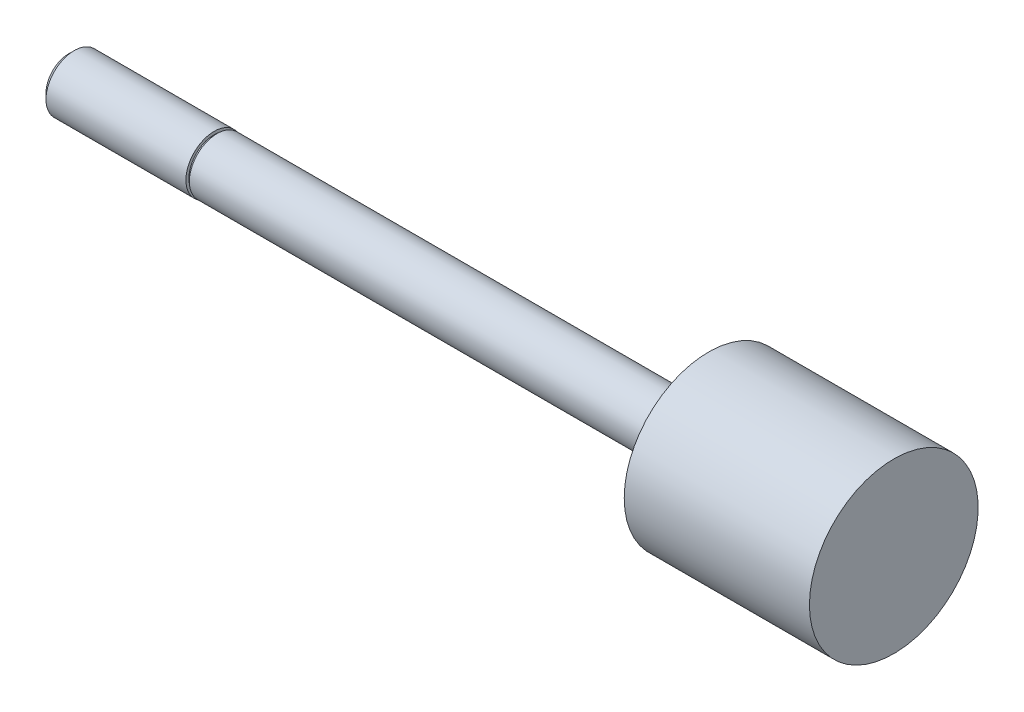
SolidWorks part; units mm, degrees
material "AISI 304"
ref_plane "Front Plane" through (0, 0, 0) normal (0, 0, 1) x (1, 0, 0)
ref_plane "Top Plane" through (0, 0, 0) normal (0, 1, 0) x (1, 0, 0)
ref_plane "Right Plane" through (0, 0, 0) normal (1, 0, 0) x (0, 0, -1)
sketch "Sketch1" plane through (0, 0, 0) normal (0, 0, 1) x (1, 0, 0)
  line L0 (0, 0) -> (0, 2.3749)
  line L1 (0, 2.3749) -> (42.0624, 2.3749)
  line L2 (42.0624, 2.3749) -> (42.0624, 7.2199)
  line L3 (42.0624, 7.2199) -> (57.912, 7.2199)
  line L4 (57.912, 7.2199) -> (57.912, 0)
  line L5 (57.912, 0) -> (0, 0)
  line L6 (57.912, 0) -> (0, 0) construction
revolve "Revolve1" add sketch "Sketch1" angle 360 about L6 reverse direction yes
sketch "Sketch2" plane through (0, 0, 0) normal (0, 0, 1) x (1, 0, 0)
  line L0 (-12.7, 0) -> (-12.7, 1.9406)
  line L1 (-12.7, 1.9406) -> (-12.2276, 2.413)
  line L2 (-12.2276, 2.413) -> (0, 2.413)
  line L3 (0, 2.413) -> (0, 0)
  line L4 (0, 0) -> (-12.7, 0)
  line L5 (0, 0) -> (-12.7, 0) construction
revolve "Revolve2" add sketch "Sketch2" angle 360 about L5 reverse direction yes
cosmetic thread "Cosmetic Thread1"
ref_plane "Plane1" through (0, 0, 0) normal (1, 0, 0) x (0, 0, -1)
ref_plane "Plane2" through (0, 0, 0) normal (1, 0, 0) x (0, 0, -1)
ref_plane "Plane3" through (99.9744, 0, 0) normal (1, 0, 0) x (0, 0, -1)
ref_plane "Plane4" through (-12.7, 0, 0) normal (1, 0, 0) x (0, 0, -1)
sketch "Sketch3" plane through (0, 0, 0) normal (0, 0, 1) x (1, 0, 0)
  line L0 (-0.254, 2.159) -> (0, 2.159)
  line L1 (0, 2.159) -> (0, 2.667)
  line L2 (0, 2.667) -> (-0.254, 2.667)
  line L3 (-0.254, 2.667) -> (-0.254, 2.159)
  line L4 (0, 0) -> (-0.254, 0) construction
revolve "Cut-Revolve1" cut sketch "Sketch3" angle 360 about L4 reverse direction yes
ref_plane "Plane5" through (0, 0, 0) normal (1, 0, 0) x (0, 0, -1)
ref_plane "Plane6" through (-12.7, 0, 0) normal (1, 0, 0) x (0, 0, -1)
ref_plane "dia1 XY" through (0, 0, 0) normal (1, 0, 0) x (0, 0, -1)
ref_plane "dia1 XZ" through (0, 2.3749, 0) normal (0, -1, 0) x (-1, 0, 0)
ref_plane "dia1 YZ" through (0, 0, 0) normal (0, 0, -1) x (-1, 0, 0)
ref_axis "dia1 X" through (0, 2.3749, 80.9) along (0, 0, -1)
ref_axis "dia1 Y" through (0, -50, 0) along (0, 1, 0)
ref_axis "dia1 Z" through (80.9, 2.3749, 0) along (-1, 0, 0)
sketch3d "dia1"
  point P0 (0, 2.3749, 0)
ref_plane "dia12 XY" through (0, 0, 0) normal (1, 0, 0) x (0, 0, -1)
ref_plane "dia12 XZ" through (0, 0, 0) normal (0, -1, 0) x (-1, 0, 0)
ref_plane "dia12 YZ" through (0, 0, 7.8105) normal (0, 0, -1) x (-1, 0, 0)
ref_axis "dia12 X" through (0, 0, 80.9) along (0, 0, -1)
ref_axis "dia12 Y" through (0, -50, 7.8105) along (0, 1, 0)
ref_axis "dia12 Z" through (80.9, 0, 7.8105) along (-1, 0, 0)
sketch3d "dia12"
  point P0 (0, 0, 7.8105)
ref_plane "dia2 XY" through (0, 0, 0) normal (1, 0, 0) x (0, 0, -1)
ref_plane "dia2 XZ" through (0, -2.3749, 0) normal (0, -1, 0) x (-1, 0, 0)
ref_plane "dia2 YZ" through (0, 0, 0) normal (0, 0, -1) x (-1, 0, 0)
ref_axis "dia2 X" through (0, -2.3749, 80.9) along (0, 0, -1)
ref_axis "dia2 Y" through (0, -50, 0) along (0, 1, 0)
ref_axis "dia2 Z" through (80.9, -2.3749, 0) along (-1, 0, 0)
sketch3d "dia2"
  point P0 (0, -2.3749, 0)
ref_plane "dia22 XY" through (0, 0, 0) normal (1, 0, 0) x (0, 0, -1)
ref_plane "dia22 XZ" through (0, 0, 0) normal (0, -1, 0) x (-1, 0, 0)
ref_plane "dia22 YZ" through (0, 0, -7.8105) normal (0, 0, -1) x (-1, 0, 0)
ref_axis "dia22 X" through (0, 0, 80.9) along (0, 0, -1)
ref_axis "dia22 Y" through (0, -50, -7.8105) along (0, 1, 0)
ref_axis "dia22 Z" through (80.9, 0, -7.8105) along (-1, 0, 0)
sketch3d "dia22"
  point P0 (0, 0, -7.8105)
ref_plane "rl1 XY" through (-12.7, 0, 0) normal (1, 0, 0) x (0, 0, -1)
ref_plane "rl1 XZ" through (0, 0, 0) normal (0, -1, 0) x (-1, 0, 0)
ref_plane "rl1 YZ" through (0, 0, 0) normal (0, 0, -1) x (-1, 0, 0)
ref_axis "rl1 X" through (-12.7, 0, 80.9) along (0, 0, -1)
ref_axis "rl1 Y" through (-12.7, -50, 0) along (0, 1, 0)
ref_axis "rl1 Z" through (80.9, 0, 0) along (-1, 0, 0)
sketch3d "rl1"
  point P0 (-12.7, 0, 0)
ref_plane "rl2 XY" through (0, 0, 0) normal (1, 0, 0) x (0, 0, -1)
ref_plane "rl2 XZ" through (0, 0, 0) normal (0, -1, 0) x (-1, 0, 0)
ref_plane "rl2 YZ" through (0, 0, 0) normal (0, 0, -1) x (-1, 0, 0)
ref_axis "rl2 X" through (0, 0, 80.9) along (0, 0, -1)
ref_axis "rl2 Y" through (0, -50, 0) along (0, 1, 0)
ref_axis "rl2 Z" through (80.9, 0, 0) along (-1, 0, 0)
sketch3d "rl2"
  point P0 (0, 0, 0)
ref_plane "rod_cp XY" through (0, 0, 0) normal (1, 0, 0) x (0, 0, -1)
ref_plane "rod_cp XZ" through (0, 0, 0) normal (0, -1, 0) x (-1, 0, 0)
ref_plane "rod_cp YZ" through (0, 0, 0) normal (0, 0, -1) x (-1, 0, 0)
ref_axis "rod_cp X" through (0, 0, 80.9) along (0, 0, -1)
ref_axis "rod_cp Y" through (0, -50, 0) along (0, 1, 0)
ref_axis "rod_cp Z" through (80.9, 0, 0) along (-1, 0, 0)
sketch3d "rod_cp"
  point P0 (0, 0, 0)
ref_plane "thd1 XY" through (-12.7, 0, 0) normal (1, 0, 0) x (0, 0, -1)
ref_plane "thd1 XZ" through (0, 2.413, 0) normal (0, -1, 0) x (-1, 0, 0)
ref_plane "thd1 YZ" through (0, 0, 0) normal (0, 0, -1) x (-1, 0, 0)
ref_axis "thd1 X" through (-12.7, 2.413, 80.9) along (0, 0, -1)
ref_axis "thd1 Y" through (-12.7, -50, 0) along (0, 1, 0)
ref_axis "thd1 Z" through (80.9, 2.413, 0) along (-1, 0, 0)
sketch3d "thd1"
  point P0 (-12.7, 2.413, 0)
ref_plane "thd2 XY" through (-12.7, 0, 0) normal (1, 0, 0) x (0, 0, -1)
ref_plane "thd2 XZ" through (0, -2.413, 0) normal (0, -1, 0) x (-1, 0, 0)
ref_plane "thd2 YZ" through (0, 0, 0) normal (0, 0, -1) x (-1, 0, 0)
ref_axis "thd2 X" through (-12.7, -2.413, 80.9) along (0, 0, -1)
ref_axis "thd2 Y" through (-12.7, -50, 0) along (0, 1, 0)
ref_axis "thd2 Z" through (80.9, -2.413, 0) along (-1, 0, 0)
sketch3d "thd2"
  point P0 (-12.7, -2.413, 0)
ref_plane "to_rod_clevis XY" through (-12.7, 0, 0) normal (1, 0, 0) x (0, 0, -1)
ref_plane "to_rod_clevis XZ" through (0, 0, 0) normal (0, -1, 0) x (-1, 0, 0)
ref_plane "to_rod_clevis YZ" through (0, 0, 0) normal (0, 0, -1) x (-1, 0, 0)
ref_axis "to_rod_clevis X" through (-12.7, 0, 80.9) along (0, 0, -1)
ref_axis "to_rod_clevis Y" through (-12.7, -50, 0) along (0, 1, 0)
ref_axis "to_rod_clevis Z" through (80.9, 0, 0) along (-1, 0, 0)
sketch3d "to_rod_clevis"
  point P0 (-12.7, 0, 0)
